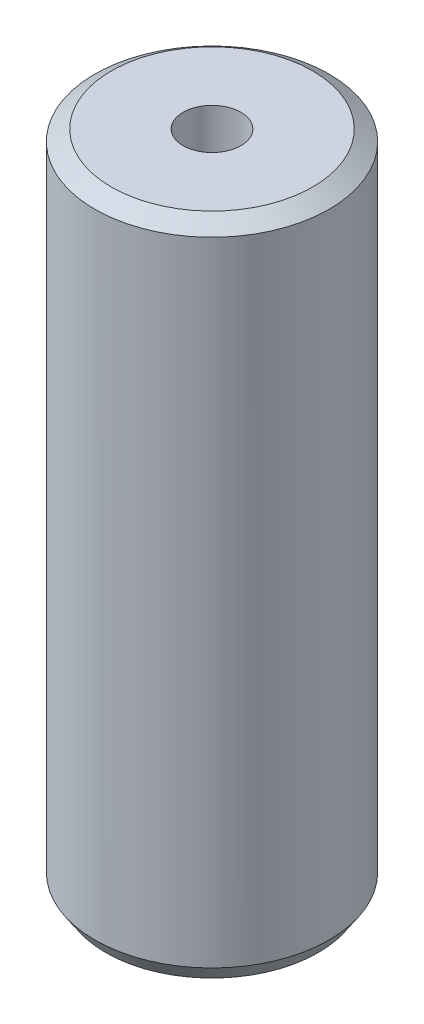
SolidWorks part; units mm, degrees
ref_plane "Front Plane" through (0, 0, 0) normal (0, 0, 1) x (1, 0, 0)
ref_plane "Top Plane" through (0, 0, 0) normal (0, 1, 0) x (1, 0, 0)
ref_plane "Right Plane" through (0, 0, 0) normal (1, 0, 0) x (0, 0, -1)
sketch "Sketch1" plane through (0, 0, 0) normal (0, 1, 0) x (1, 0, 0)
  circle A0 centre (0, 0) radius 5
  dimension "SHAFT_OD" = 10
extrude "Boss-Extrude1" add sketch "Sketch1" along normal blind 28.1819
sketch "Sketch2" plane through (0, 0, 0) normal (0, 1, 0) x (1, 0, 0)
  circle A0 centre (0, 0) radius 1.2347
  dimension "BORE_D" = 2.4694
extrude "Cut-Extrude1" cut sketch "Sketch2" along normal through all
chamfer "Chamfer1" distance 0.4692 angle 56.355 2 edges at (0, 28.1819, 5) (0, 0, 5) first distance on face at (0, 28.1819, 5) first distance on face at (0, 0, 1.2347)
